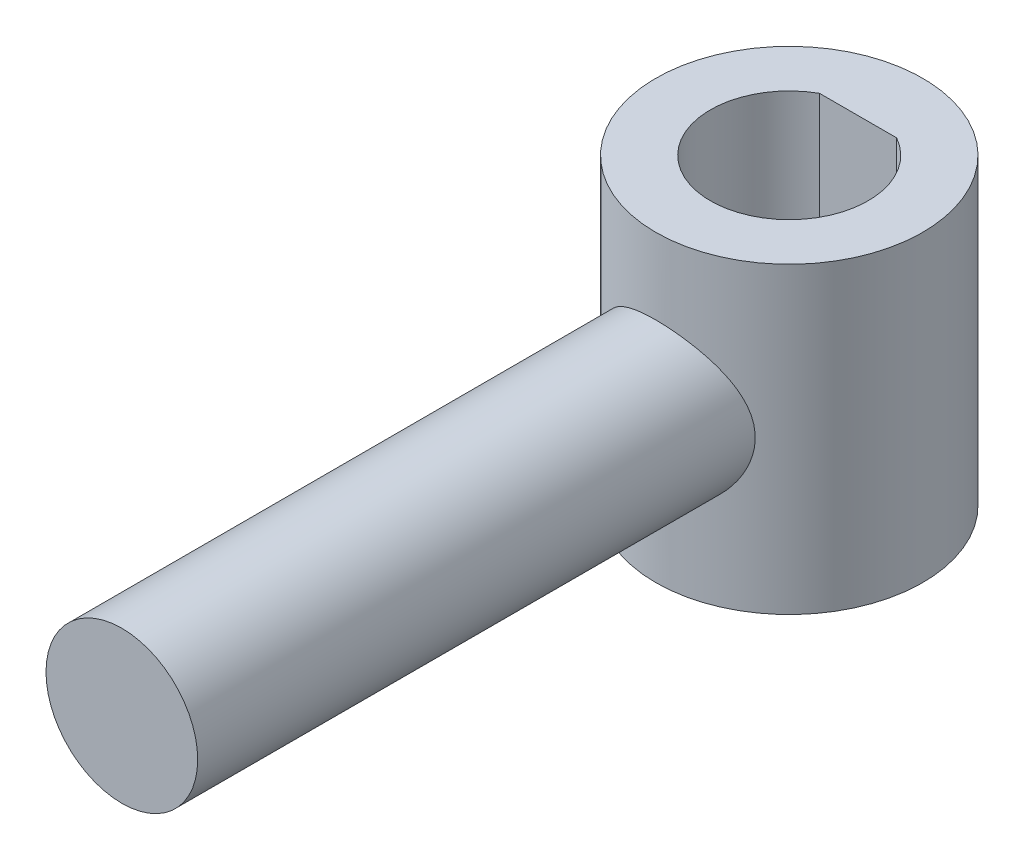
SolidWorks part; units mm, degrees
material "ABS"
ref_plane "Front Plane" through (0, 0, 0) normal (0, 0, 1) x (1, 0, 0)
ref_plane "Top Plane" through (0, 0, 0) normal (0, 1, 0) x (1, 0, 0)
ref_plane "Right Plane" through (0, 0, 0) normal (1, 0, 0) x (0, 0, -1)
sketch "Sketch1" plane through (0, 0, 0) normal (0, 1, 0) x (1, 0, 0)
  line L0 (3.175, 5.6718) -> (-3.175, 5.6718)
  arc A0 (-3.175, 5.6718) -> (3.175, 5.6718) centre (0, 0) ccw
  circle A1 centre (0, 0) radius 11
  dimension "D1" = 13
  dimension "D2" = 4.5
  dimension "D3" = 6.35
sketch "Sketch2" plane through (0, 0, 0) normal (0, 0, 1) x (1, 0, 0)
  circle A0 centre (0, 0) radius 6.25
  dimension "D1" = 12.5
extrude "Boss-Extrude3" add sketch "Sketch2" along normal blind 55 contours A0
extrude "Boss-Extrude4" add sketch "Sketch1" along normal mid plane 25 contours A1
extrude "Cut-Extrude1" cut sketch "Sketch1<4>" against normal through all both and the other way through all contours A0 L0
sketch "Sketch1<4>" plane through (0, 0, 0) normal (0, 1, 0) x (1, 0, 0) same geometry as "Sketch1"
ref_plane "Plane1" through (0, 0, 45) normal (0, 0, 1) x (1, 0, 0)
sketch "Sketch3" plane through (0, 0, 45) normal (0, 0, 1) x (1, 0, 0)
  line L0 (-3.175, -5.3835) -> (3.175, -5.3835)
  circle A2 centre (0, 0) radius 6.25 construction
  arc A3 (3.175, -5.3835) -> (-3.175, -5.3835) centre (0, 0) cw
  point P3 (0, -5.3835)
  dimension "D1" = 6.35
extrude "Cut-Extrude2" cut sketch "Sketch3" against normal mid plane 4.7
